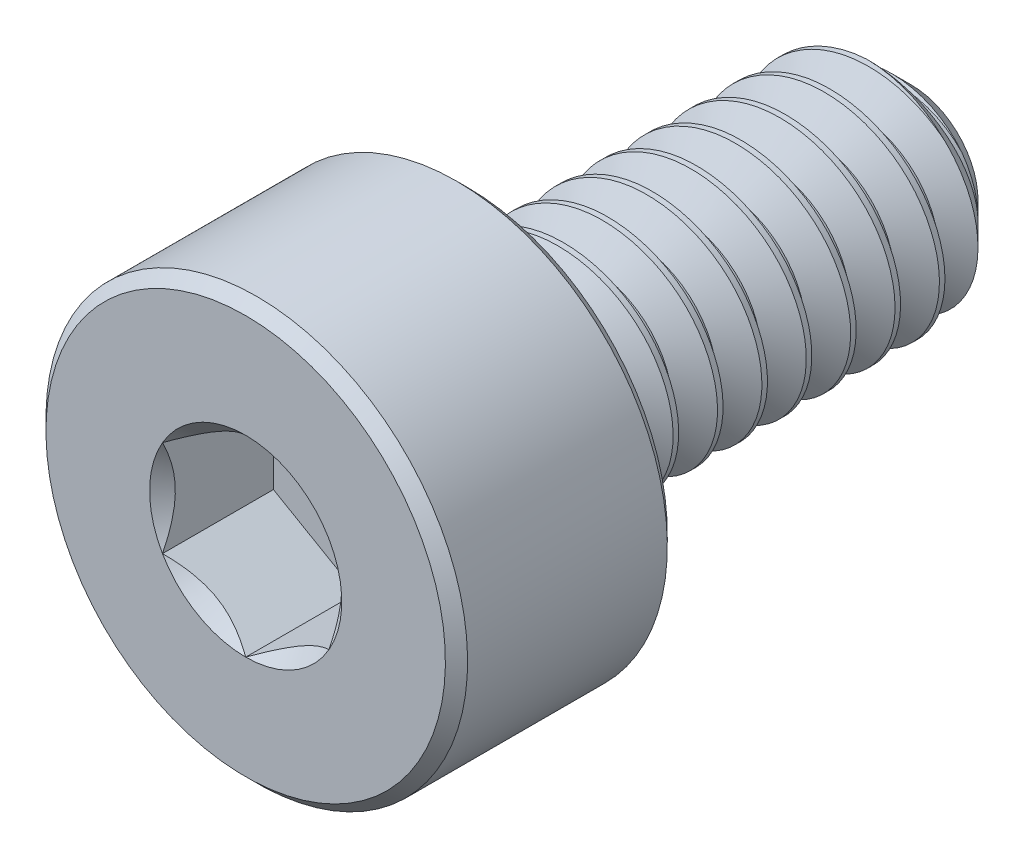
SolidWorks part; units mm, degrees
ref_plane "Front Plane" through (0, 0, 0) normal (0, 0, 1) x (1, 0, 0)
ref_plane "Top Plane" through (0, 0, 0) normal (0, 1, 0) x (1, 0, 0)
ref_plane "Right Plane" through (0, 0, 0) normal (1, 0, 0) x (0, 0, -1)
sketch "Sketch1" plane through (0, 0, 0) normal (1, 0, 0) x (0, 0, -1)
  line L0 (-3, 0) -> (3, 0) construction
  line L1 (3, 0) -> (3, 0.6) construction
  line L2 (3, 0.6) -> (2.6, 1) construction
  line L3 (2.6, 1) -> (2.7, 1) construction
  line L4 (2.7, 1) -> (-1, 1) construction
  line L5 (-1, 1) -> (-1, 1.9) construction
  line L6 (-1, 1.9) -> (-3, 1.9) construction
  line L7 (-3, 1.9) -> (-3, 0) construction
  line L8 (3, 0.6) -> (3, 1) construction
  line L9 (2.975, 1.0433) -> (3.175, 0.6969) construction
  line L10 (3.175, 0.6969) -> (3.375, 1.0433) construction
  line L11 (3.375, 1.0433) -> (2.975, 1.0433) construction
  line L12 (3.175, 1.0433) -> (3.175, 1) construction
  line L13 (3.175, 0.6969) -> (3.175, 0.7402) construction
  line L14 (3.15, 0.7402) -> (3.2, 0.7402) construction
  line L15 (3, 1) -> (3.35, 1) construction
  line L16 (2.9875, 1.0217) -> (3.3625, 1.0217) construction
  line L17 (3, 0) -> (3, -1) construction
  line L18 (-1.1, 1.9) -> (-1, 1.8) construction
  line L19 (-2.9, 1.9) -> (-3, 1.8) construction
  line L20 (-1, 1) -> (-1, 0) construction
  line L21 (-1, 0.5) -> (0.3333, 0.5) construction
  line L22 (0.3333, 0.5) -> (1.6667, 0.5) construction
  line L23 (1.6667, 0.5) -> (3, 0.5) construction
  line L24 (0.3333, 0.5) -> (0.3333, 1) construction
  line L25 (0.3333, 1) -> (0.3333, 1.9) construction
  line L26 (1.6667, 0.5) -> (1.6667, 1.9) construction
  point P0 (-3, 0.75)
  point P3 (2, 1)
  point P4 (0, 0)
  point P18 (1.6667, 1)
  point P22 (3.175, 0.7402)
  point P24 (2.7, 1)
  point P25 (3.175, 1)
  point P28 (3.175, 1.0217)
  point P29 (2, -1)
  point P30 (0.3333, 1)
  point P31 (-2, 1.9)
  point P37 (-1.35, 1.9)
  point P38 (-2.85, 1.9)
  point P45 (0.3333, 0.5)
  point P46 (1.6667, 0.5)
  dimension "D1" = 45
  dimension "D2" = 0.05
  dimension "D3" = 0.4
  dimension "D7" = 0.1
  dimension "D8" = 0.1
  dimension "D9" = 0.1
  dimension "D10" = 0.05
  dimension "D11" = 0.25
  dimension "Drive Size" = 1.5
  dimension "Head Diameter" = 3.8
  dimension "Head Height" = 2
  dimension "Thread Pitch" = 0.4
  dimension "Thread Major Diameter" = 2
  dimension "Length" = 4
  dimension "D12" = 0.3
  dimension "D4" = 1
sketch "Sketch2" plane through (0, 0, 0) normal (1, 0, 0) x (0, 0, -1)
  line L0 (-3, 0) -> (-3, 1.8)
  line L1 (-2.9, 1.9) -> (-1.1, 1.9)
  line L2 (-1, 1.8) -> (-1, 1)
  line L3 (-1, 1) -> (2.6, 1)
  line L4 (2.6, 1) -> (3, 0.6)
  line L5 (3, 0.6) -> (3, 0)
  line L6 (-1.1, 1.9) -> (-1, 1.8) construction
  line L7 (3, 0) -> (-3, 0)
  line L8 (-2.9, 1.9) -> (-3, 1.8) construction
  line L9 (-1.1, 1.9) -> (-1, 1.8)
  line L10 (-2.9, 1.9) -> (-3, 1.8)
revolve "Revolve1" add sketch "Sketch2" angle 360 about L7
sketch "Sketch3" plane through (0, 0, 3) normal (0, 0, 1) x (1, 0, 0)
  line L1 (0.75, -0.433) -> (0.75, 0.433)
  line L2 (0.75, 0.433) -> (0, 0.866)
  line L3 (0, 0.866) -> (-0.75, 0.433)
  line L4 (-0.75, 0.433) -> (-0.75, -0.433)
  line L5 (-0.75, -0.433) -> (0, -0.866)
  line L6 (0, -0.866) -> (0.75, -0.433)
  circle A0 centre (0, 0) radius 0.75 construction
extrude "Cut-Extrude1" cut sketch "Sketch3" against normal offset from surface (1 mm away) 1 up to face at (0, 1.8, 1)
sketch "Sketch4" plane through (0, 0, 3) normal (0, 0, 1) x (1, 0, 0)
  circle A0 centre (0, 0) radius 0.866
extrude "Cut-Extrude2" cut sketch "Sketch4" against normal up to vertex (1 mm away) draft 45 up to point (0, 1.9, 2)
ref_plane "Plane1" through (0, 0, -2.7) normal (0, 0, 1) x (1, 0, 0)
split "Split1" bodies to split 106 resulting bodies 107 108 split by face at (0, 1.8, 1)
sketch "Sketch6" plane through (0, 0, -3) normal (0, 0, -1) x (-1, 0, 0)
  circle A0 centre (0, 0) radius 1
curve "Helix/Spiral1" pitch 0.4 height 4.46 radius 1 centre (0, 0, -3) axis (0, 0, 1) start towards (0, 1, 0)
sketch "Sketch7" plane through (0, 0, 0) normal (1, 0, 0) x (0, 0, -1)
  line L0 (2.9875, 1.0217) -> (3.3625, 1.0217)
  line L1 (3.3625, 1.0217) -> (3.2, 0.7402)
  line L2 (3.2, 0.7402) -> (3.15, 0.7402)
  line L3 (3.15, 0.7402) -> (2.9875, 1.0217)
sweep "Cut-Sweep1" cut profiles "Sketch7" path "Helix/Spiral1" align with end faces yes
sketch "Sketch8" plane through (0, 0, 1) normal (0, 0, -1) x (-1, 0, 0)
  circle A0 centre (0, 0) radius 1
extrude "Boss-Extrude1" add sketch "Sketch8" along normal through all draft 45
equation "\"D2@Sketch1\" = \"Thread Pitch@Sketch1\" / 8"
equation "\"D3@Sketch1\"= \"Thread Pitch@Sketch1\""
equation "\"D4@Helix/Spiral1\" = \"Thread Pitch@Sketch1\""
equation "\"D7@Sketch1\" = \"Head Height@Sketch1\" * .05"
equation "\"D8@Sketch1\"=\"D7@Sketch1\""
equation "\"D9@Sketch1\"=\"D7@Sketch1\""
equation "\"D10@Sketch1\"=\"D7@Sketch1\"/2"
equation "\"D11@Sketch1\"=\"D10@Sketch1\"*5"
equation "\"D4@Sketch1\"=\"Thread Pitch@Sketch1\"*2.5"
equation "\"D12@Sketch1\"=\"Thread Pitch@Sketch1\"*.75"
